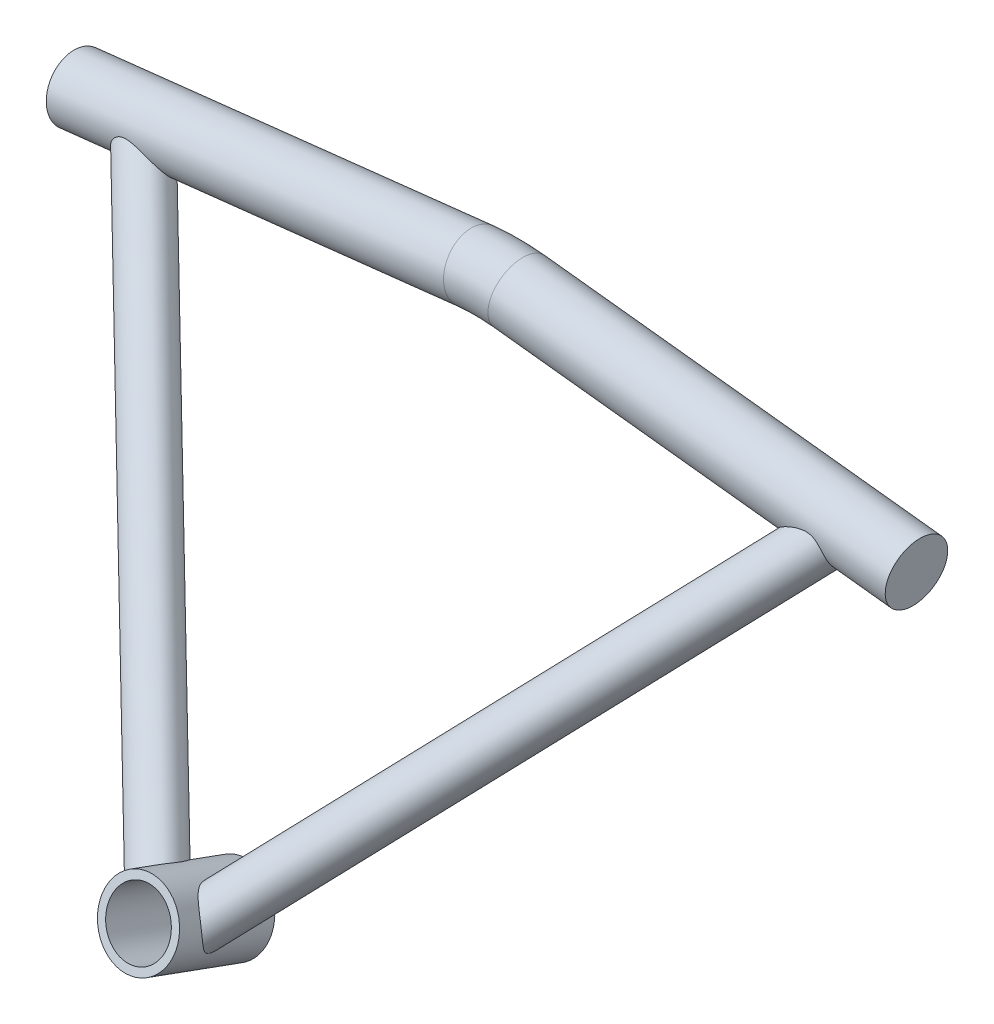
SolidWorks part; units mm, degrees
material "AISI 4130 Steel, normalized at 870C"
ref_plane "Front Plane" through (0, 0, 0) normal (0, 0, 1) x (1, 0, 0)
ref_plane "Top Plane" through (0, 0, 0) normal (0, 1, 0) x (1, 0, 0)
ref_plane "Right Plane" through (0, 0, 0) normal (1, 0, 0) x (0, 0, -1)
sketch "Sketch3" plane through (0, 0, 0) normal (0, 1, 0) x (1, 0, 0)
  line L0 (-5.08, -6.35) -> (5.08, -6.35) construction
  line L2 (0, -88.2205) -> (0, 88.2205) construction
  line L3 (5.08, 0) -> (-5.08, 0) construction
  dimension "D1" = 5.08
  dimension "D2" = 10.16
  dimension "D3" = 6.35
  dimension "D4" = 10.16
  dimension "D5" = 5.08
ref_plane "Plane1" through (0, 3.1576, 3.5069) normal (0, 0.6691, 0.7431) x (1, 0, 0)
ref_plane "Plane3" through (0, 0, 0) normal (0, 0.342, 0.9397) x (-1, 0, 0)
sketch "Sketch1" plane through (0, 0, 0) normal (0, 0.342, 0.9397) x (1, 0, 0)
  circle A0 centre (0, 0) radius 15.875
  dimension "D1" = 31.75
extrude "Boss-Extrude1" add sketch "Sketch1" along normal mid plane 41.402 contours A0
sketch "Sketch4" plane through (0, 3.1576, 3.5069) normal (0, 0.6691, 0.7431) x (1, 0, 0)
  line L0 (-5.08, -4.249) -> (-143.484, 193.4124)
  line L2 (0, -91.1467) -> (0, 91.1467) construction
  dimension "D2" = 35
  dimension "D3" = 241.3
sweep "Sweep1" add path "Sketch4" circular profile diameter 19.05 parameters "D3"=19.05
sketch "Sketch15" plane through (0, 3.1576, 3.5069) normal (0, 0.6691, 0.7431) x (1, 0, 0)
  line L0 (5.08, -4.249) -> (143.484, 193.4124)
  line L1 (0, -91.1467) -> (0, 91.1467) construction
  dimension "D1" = 241.3
  dimension "D2" = 35
sweep "Sweep2" add path "Sketch15" circular profile diameter 19.05 parameters "D3"=19.05
sketch "Sketch36" plane through (-138.0789, 146.546, -131.9506) normal (-0.5736, 0.6087, -0.5481) x (0.819, 0.4396, -0.3688)
  circle A0 centre (-6.5025, -4.8502) radius 7.9375
  dimension "D1" = 15.875
extrude "Cut-Extrude2" cut sketch "Sketch36" against normal up to surface (251.5545 mm away) up to face at (15.2222, -2.9096, 5.1794)
sketch "Sketch37" plane through (138.0789, 146.546, -131.9506) normal (0.5736, 0.6087, -0.5481) x (0.819, -0.4396, 0.3688)
  circle A0 centre (6.5025, -4.8502) radius 7.9375
  dimension "D1" = 15.875
extrude "Cut-Extrude3" cut sketch "Sketch37" against normal up to surface (226.8273 mm away) up to face at (10.6847, -5.6391, 18.8354)
sketch "Sketch77" plane through (0, 7.0802, 19.4526) normal (0, 0.342, 0.9397) x (1, 0, 0)
  circle A1 centre (0, 0) radius 15.875
extrude "Boss-Extrude2" add sketch "Sketch77" against normal up to surface (41.402 mm away) up to face at (0, -21.9978, -14.023)
sketch "Sketch2" plane through (0, -7.0802, -19.4526) normal (0, -0.342, -0.9397) x (-1, 0, 0)
  circle A0 centre (0, 0) radius 12.7
  dimension "D1" = 25.4
extrude "Cut-Extrude1" cut sketch "Sketch2" against normal up to next
ref_plane "Plane2" through (0, 0, -127) normal (0, 0, 1) x (1, 0, 0)
sketch "Sketch40" plane through (-106.934, 0, -127) normal (0, 0, 1) x (1, 0, 0)
  line L2 (106.934, -87.3181) -> (106.934, 87.3181) construction
  line L3 (97.8738, 162.0535) -> (-64.4304, 143.8481)
  line L4 (115.9942, 162.0535) -> (278.2984, 143.8481)
  arc A0 (97.8738, 162.0535) -> (115.9942, 162.0535) centre (106.934, 81.28) cw
  point P0 (106.934, 162.56)
  point P4 (0, 0)
  point P7 (106.934, 162.56)
  point P9 (0, 0)
  dimension "D1" = 163.322
  dimension "D3" = 81.28
  dimension "D2" = 163.322
  dimension "D4" = 6.4
sweep "Sweep3" add path "Sketch40" circular profile diameter 25.4 parameters "D3"=25.4
